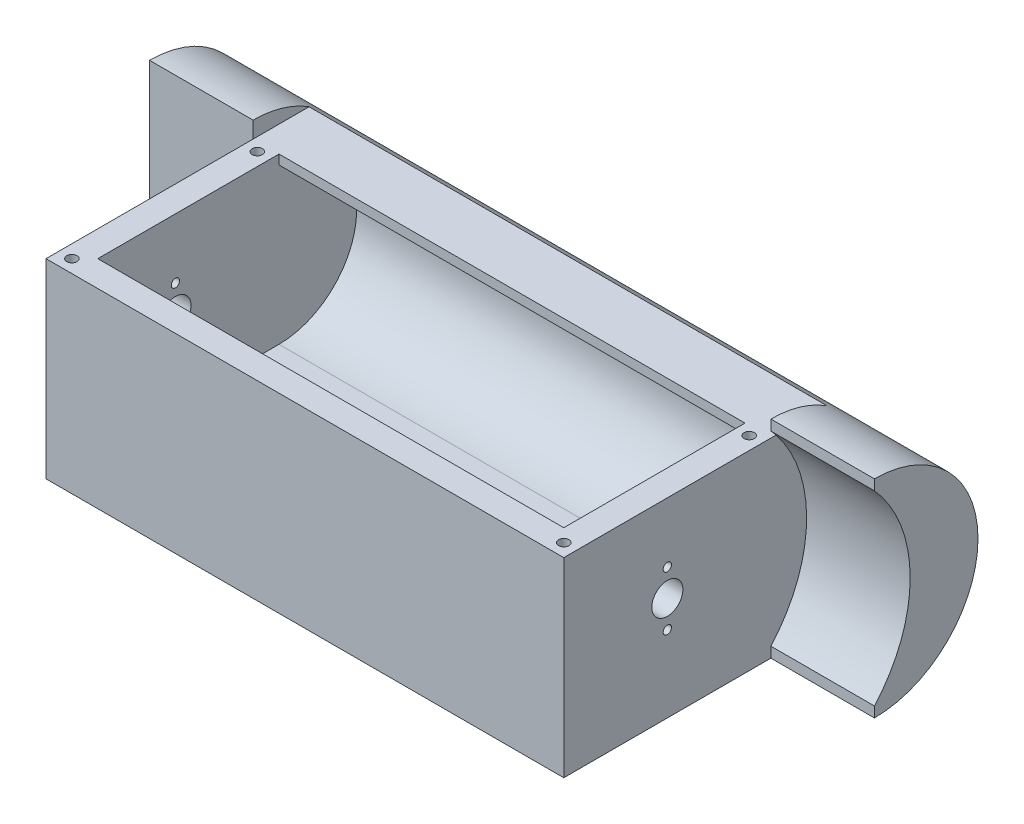
SolidWorks part; units mm, degrees
ref_plane "Front Plane" through (0, 0, 0) normal (0, 0, 1) x (1, 0, 0)
ref_plane "Top Plane" through (0, 0, 0) normal (0, 1, 0) x (1, 0, 0)
ref_plane "Right Plane" through (0, 0, 0) normal (1, 0, 0) x (0, 0, -1)
sketch "Sketch1" plane through (0, 0, 0) normal (1, 0, 0) x (0, 0, -1)
  line L1 (-20, 20) -> (20, 20)
  line L2 (-20, 20) -> (-20, -20)
  line L3 (-20, -20) -> (20, -20)
  arc A0 (20, 20) -> (20, -20) centre (20, 0) cw
  dimension "D1" = 40
  dimension "D2" = 40
  dimension "D3" = 20
  dimension "D4" = 20
extrude "Boss-Extrude1" add sketch "Sketch1" along normal blind 100
shell "Shell3" thickness 5 removed face at (50, 20, 0)
sketch "Sketch9" plane through (100, 0, 0) normal (1, 0, 0) x (0, 0, -1)
  line L0 (20, 20) -> (20, -20)
  arc A0 (20, 20) -> (20, -20) centre (20, 0) cw
  arc A1 (20, -20) -> (20, 20) centre (20, 0) ccw construction
extrude "Boss-Extrude2" add sketch "Sketch9" along normal blind 20
ref_plane "Plane1" through (50, 0, 0) normal (1, 0, 0) x (0, 0, -1)
mirror "Mirror1" about plane through (50, 0, 0) normal (1, 0, 0) of "Boss-Extrude2"
sketch "Sketch7" plane through (0, 20, 0) normal (0, 1, 0) x (1, 0, 0)
  line L0 (0, 20) -> (0, 0) construction
  line L1 (0, 30.81) -> (100, 30.81)
  line L2 (0, 30.81) -> (0, -20)
  line L3 (0, -20) -> (100, -20)
  line L4 (100, 30.81) -> (100, -20)
  dimension "D1" = 50.81
extrude "Cut-Extrude6" cut sketch "Sketch7" against normal blind 3.175
sketch "Sketch2" plane through (100, 0, 0) normal (1, 0, 0) x (0, 0, -1)
  line L0 (0, 16.825) -> (0, -20) construction
  line L2 (-20, -20) -> (20, -20) construction
  line L3 (-20, 0) -> (40, 0) construction
  line L4 (-20, 16.825) -> (-20, -20) construction
  line L5 (-20, 16.825) -> (20, 16.825) construction
  circle A0 centre (0, -5.25) radius 0.8
  circle A1 centre (0, 0) radius 3
  circle A2 centre (0, 5.25) radius 0.8
  arc A4 (20, -20) -> (30.8129, 16.825) centre (20, 0) ccw construction
  dimension "D1" = 6
  dimension "D2" = 1.6
  dimension "D3" = 5.25
extrude "Cut-Extrude1" cut sketch "Sketch2" against normal up to surface (100 mm away) up to face at (0, -1.5875, 0)
sketch "Sketch8" plane through (0, 16.825, 0) normal (0, 1, 0) x (1, 0, 0)
  line L0 (0, -20) -> (100, -20) construction
  line L1 (100, -20) -> (100, 20) construction
  line L2 (50, -20) -> (50, 40) construction
  line L3 (120, 40) -> (-20, 40) construction
  circle A0 centre (97.5, -17.5) radius 1
  circle A1 centre (97.5, 18.31) radius 1
  circle A2 centre (2.5, -17.5) radius 1
  circle A3 centre (2.5, 18.31) radius 1
  dimension "D1" = 2
  dimension "D2" = 2.5
  dimension "D3" = 2.5
  dimension "D4" = 35.81
  dimension "D5" = 2.5
extrude "Cut-Extrude7" cut sketch "Sketch8" against normal blind 3
sketch "Sketch10" plane through (120, 0, 0) normal (1, 0, 0) x (0, 0, -1)
  line L0 (20, 17.9892) -> (20, -17.9892)
  line L1 (20, 20) -> (20, -20) construction
  arc A0 (20, -17.9892) -> (20, 17.9892) centre (0, 0) ccw
  dimension "D1" = 53.8
extrude "Cut-Extrude8" cut sketch "Sketch10" against normal up to surface (20 mm away) up to face at (100, -5.25, 0.8)
